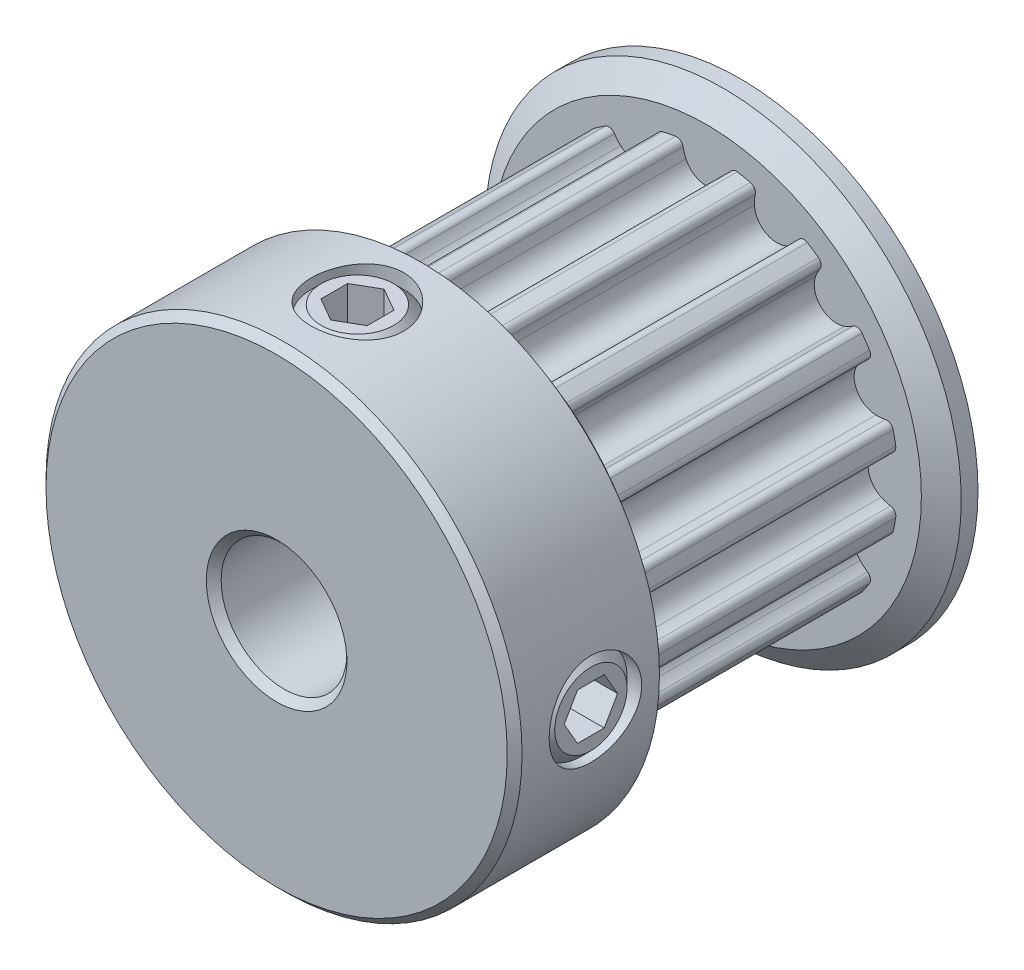
SolidWorks part; units mm, degrees
ref_plane "Front Plane" through (0, 0, 0) normal (0, 0, 1) x (1, 0, 0)
ref_plane "Top Plane" through (0, 0, 0) normal (0, 1, 0) x (1, 0, 0)
ref_plane "Right Plane" through (0, 0, 0) normal (1, 0, 0) x (0, 0, -1)
sketch "Sketch1" plane through (0, 0, 0) normal (0, 0, 1) x (1, 0, 0)
  line L1 (-2.553, 6.1245) -> (2.553, 6.1245) construction
  line L4 (0, 0) -> (0, 6.1245) construction
  line L5 (0, 6.1245) -> (0, 12.0565) construction
  line L6 (0, 7.6455) -> (2.9417, 7.0569) construction
  line L7 (2.9417, 7.0569) -> (3.8741, 6.6682) construction
  line L8 (2.9417, 7.0569) -> (2.553, 6.1245) construction
  line L9 (-2.9417, 7.0569) -> (-2.553, 6.1245) construction
  line L10 (-2.7951, 6.7052) -> (-3.7579, 9.015)
  line L11 (-3.7579, 9.015) -> (3.7579, 9.015)
  line L12 (3.7579, 9.015) -> (2.7951, 6.7052)
  circle A0 centre (0, 0) radius 7.6455 construction
  circle A1 centre (0, 0) radius 9.015 construction
  circle A2 centre (0, 0) radius 7.2645 construction
  arc A3 (-0.7739, 6.6229) -> (0.7739, 6.6229) centre (0, 6.9745) ccw
  arc A4 (-0.7739, 6.6229) -> (-0.8836, 6.9694) centre (0.61, 7.2516) cw
  arc A5 (-2.7951, 6.7052) -> (-1.1695, 7.1697) centre (0, 0) cw
  arc A6 (-0.8836, 6.9694) -> (-1.1695, 7.1697) centre (-1.1292, 6.923) ccw
  arc A7 (2.7951, 6.7052) -> (1.1695, 7.1697) centre (0, 0) ccw
  arc A8 (0.8836, 6.9694) -> (1.1695, 7.1697) centre (1.1292, 6.923) cw
  arc A9 (0.7739, 6.6229) -> (0.8836, 6.9694) centre (-0.61, 7.2516) ccw
  point P6 (0, 20.9083)
  point P11 (0, 7.6455)
  point P13 (0, 9.015)
  point P14 (0, 7.2645)
  dimension "D1" = 8.8518
  dimension "D2" = 4.411
sketch "Sketch2" plane through (0, 0, 0) normal (1, 0, 0) x (0, 0, -1)
  line L0 (-8.775, 2.3812) -> (8.775, 2.3812)
  line L1 (-8.775, 2.3812) -> (-8.775, 9.015)
  line L2 (-3.29, 9.015) -> (-8.775, 9.015)
  line L3 (-3.925, 2.3813) -> (-3.925, 9.015) construction
  line L4 (-3.925, 9.015) -> (-2.655, 9.015) construction
  line L5 (-2.655, 9.015) -> (-2.655, 7.2645) construction
  line L6 (-2.655, 7.2645) -> (7.505, 7.2645)
  line L7 (7.505, 7.2645) -> (7.505, 9.015) construction
  line L8 (7.505, 9.015) -> (8.775, 9.015) construction
  line L9 (8.775, 9.015) -> (8.775, 2.3812)
  line L10 (-8.775, 0) -> (8.775, 0) construction
  line L11 (8.14, 9.015) -> (7.505, 8.1398)
  line L12 (-2.655, 8.1398) -> (-3.29, 9.015)
  line L14 (-2.655, 8.1398) -> (-2.655, 7.2645)
  line L15 (7.505, 7.2645) -> (7.505, 8.1398)
  line L16 (8.14, 9.015) -> (8.775, 9.015)
  arc A0 (-2.655, 8.1398) -> (-3.29, 9.015) centre (-3.5757, 8.1398) ccw construction
  arc A1 (7.505, 8.1398) -> (8.14, 9.015) centre (8.4257, 8.1398) cw construction
  point P12 (-2.655, 8.1398)
  point P14 (-3.29, 9.015)
  point P20 (7.505, 8.1398)
  point P21 (8.14, 9.015)
  point P25 (7.505, 0)
  point P26 (-2.655, 0)
  dimension "OA" = 17.55
  dimension "Bore" = 4.7625
  dimension "Outside Width" = 11.43
  dimension "Inside Width" = 10.16
revolve "Revolve1" add sketch "Sketch2" angle 360 mid plane about L10
sketch "Sketch3" plane through (0, 0, 0) normal (0, 0, 1) x (1, 0, 0)
  line L6 (3.7579, 9.015) -> (-3.7579, 9.015)
  line L7 (2.7951, 6.7052) -> (3.7579, 9.015)
  line L8 (-3.7579, 9.015) -> (-2.7951, 6.7052)
  line L9 (3.7579, 9.015) -> (-3.7579, 9.015)
  line L10 (2.7951, 6.7052) -> (3.7579, 9.015)
  line L11 (-3.7579, 9.015) -> (-2.7951, 6.7052)
  arc A8 (2.7951, 6.7052) -> (1.1695, 7.1697) centre (0, 0) ccw
  arc A9 (1.1695, 7.1697) -> (0.8836, 6.9694) centre (1.1292, 6.923) ccw
  arc A10 (0.7739, 6.6229) -> (0.8836, 6.9694) centre (-0.61, 7.2516) ccw
  arc A11 (-0.7739, 6.6229) -> (0.7739, 6.6229) centre (0, 6.9745) ccw
  arc A12 (-0.8836, 6.9694) -> (-0.7739, 6.6229) centre (0.61, 7.2516) ccw
  arc A13 (-0.8836, 6.9694) -> (-1.1695, 7.1697) centre (-1.1292, 6.923) ccw
  arc A14 (-1.1695, 7.1697) -> (-2.7951, 6.7052) centre (0, 0) ccw
  arc A15 (2.7951, 6.7052) -> (1.1695, 7.1697) centre (0, 0) ccw
  arc A16 (1.1695, 7.1697) -> (0.8836, 6.9694) centre (1.1292, 6.923) ccw
  arc A17 (0.7739, 6.6229) -> (0.8836, 6.9694) centre (-0.61, 7.2516) ccw
  arc A18 (-0.7739, 6.6229) -> (0.7739, 6.6229) centre (0, 6.9745) ccw
  arc A19 (-0.8836, 6.9694) -> (-0.7739, 6.6229) centre (0.61, 7.2516) ccw
  arc A20 (-0.8836, 6.9694) -> (-1.1695, 7.1697) centre (-1.1292, 6.923) ccw
  arc A21 (-1.1695, 7.1697) -> (-2.7951, 6.7052) centre (0, 0) ccw
  dimension "D1" = 0
extrude "Cut-Extrude1" cut sketch "Sketch3" against normal up to vertex (7.505 mm away) from vertex up to point (0, 7.2645, -7.505) starting at point (0, 7.2645, 2.655)
pattern_circular "CirPattern1" count 16 over 360 about axis through (0, 0, 8.775) along (0, 0, 1) of "Cut-Extrude1"
sketch "Sketch4" plane through (0, 0, 0) normal (1, 0, 0) x (0, -1, 0)
  line L0 (0, -2.655) -> (0, -8.775) construction
  line L1 (-2.3812, -8.775) -> (2.3812, -8.775) construction
  line L2 (8.1398, -2.655) -> (-8.1398, -2.655) construction
  circle A0 centre (0, -5.715) radius 1.7526
extrude "Cut-Extrude2" cut sketch "Sketch4" along normal through all
ref_plane "Plane1" through (0, 0, 5.715) normal (0, 0, 1) x (1, 0, 0)
sketch "Sketch5" plane through (0, 0, 5.715) normal (0, 0, 1) x (1, 0, 0)
  line L0 (0, 0) -> (0, 9.015) construction
  line L1 (2.3812, -1.3716) -> (2.3812, 0)
  line L2 (2.7622, -1.7526) -> (8.462, -1.7526)
  line L3 (2.3812, 0) -> (9.015, 0) construction
  line L4 (2.3812, 0) -> (8.843, 0)
  line L5 (8.843, 0) -> (8.843, -1.3716)
  line L6 (2.7622, -1.7526) -> (2.3812, -1.3716)
  line L7 (8.843, -1.3716) -> (8.462, -1.7526)
  circle A0 centre (0, 0) radius 9.015 construction
  circle A1 centre (0, 0) radius 2.3812 construction
  point P2 (2.3812, -1.7526)
  point P11 (8.843, -1.7526)
revolve "Revolve2" add sketch "Sketch5" angle 360 mid plane about L4
sketch "Sketch6" plane through (8.843, 5.3841, 0) normal (-1, 0, 0) x (0, -1, 0)
  line L1 (5.3841, 6.7269) -> (4.5078, 6.2209)
  line L2 (4.5078, 6.2209) -> (4.5078, 5.2091)
  line L3 (4.5078, 5.2091) -> (5.3841, 4.7031)
  line L4 (5.3841, 4.7031) -> (6.2604, 5.2091)
  line L5 (6.2604, 5.2091) -> (6.2604, 6.2209)
  line L6 (6.2604, 6.2209) -> (5.3841, 6.7269)
  circle A0 centre (5.3841, 5.715) radius 0.8763 construction
  dimension "D1" = 1.7526
extrude "Cut-Extrude3" cut sketch "Sketch6" along normal blind 1.3144
pattern_circular "CirPattern3" count 2 over 90 about axis through (0, 0, 8.775) along (0, 0, 1) of "Cut-Extrude2", "Revolve2", "Cut-Extrude3"
chamfer "Chamfer1" distance 0.2807 angle 45 2 edges at (2.3812, 0, 8.775) (9.015, 0, 8.775)
ref_axis "Center Axis 1" through (0, 0, -8.775) along (0, 0, 1)
ref_plane "Contact Plane 1" through (0, 0, 8.775) normal (0, 0, 1) x (1, 0, 0)
ref_plane "Contact Plane 2" through (0, 0, -8.775) normal (0, 0, -1) x (-1, 0, 0)
equation "\"D2@Sketch1\"= \"D1@Sketch1\" / 2"
equation "\"D1@Sketch6\" = \"Set Screw@Sketch4\" / 2"
equation "\"D1@Cut-Extrude3\" = \"D1@Sketch6\"*.75"
